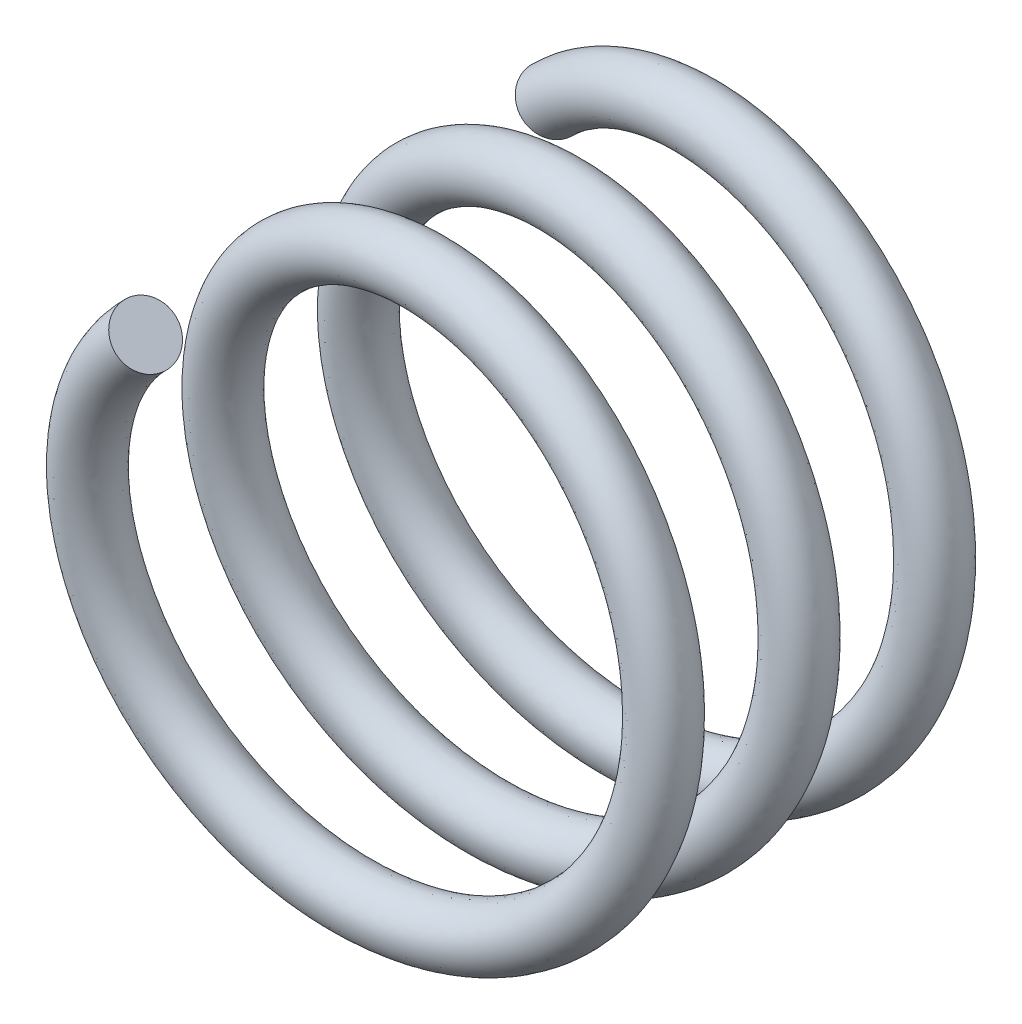
SolidWorks part; units mm, degrees
ref_plane "Front Plane" through (0, 0, 0) normal (0, 0, 1) x (1, 0, 0)
ref_plane "Top Plane" through (0, 0, 0) normal (0, 1, 0) x (1, 0, 0)
ref_plane "Right Plane" through (0, 0, 0) normal (1, 0, 0) x (0, 0, -1)
sketch "Sketch1" plane through (0, 0, 0) normal (0, 0, 1) x (1, 0, 0)
  circle A0 centre (0, 0) radius 4.36
  dimension "D1" = 8.72
curve "Helix/Spiral1" pitch 2.3333 height 7 radius 4.36 left hand yes centre (0, 0, 0) axis (0, 0, 1) start towards (-0.7071, 0.7071, 0)
ref_plane "Plane2" through (-3.083, 3.083, 0) normal (0.7046, 0.7046, 0.0849) x (0.7089, -0.6933, -0.1299)
sketch "Sketch3" plane through (-3.083, 3.083, 0) normal (0.7046, 0.7046, 0.0849) x (0.7089, -0.6933, -0.1299)
  circle A0 centre (0, 0) radius 0.5
sweep "Sweep1" add profiles "Sketch3" path "Helix/Spiral1"
ref_plane "Plane3" through (0, 0, 0) normal (0, 0, 1) x (1, 0, 0)
ref_plane "Plane4" through (0, 0, 7) normal (0, 0, 1) x (1, 0, 0)
ref_plane "Plane5" through (0, 0, 7.5) normal (0, 0, 1) x (1, 0, 0)
ref_plane "Plane6" through (0, 0, -0.5) normal (0, 0, 1) x (1, 0, 0)
equation "\"spring_diameter\"=8.72"
equation "\"coil_diameter\"=1.00"
equation "\"number_of_coils\"=3"
equation "\"D1@Sketch1\"=\"spring_diameter\""
equation "\"spring_length\"=7"
equation "\"D3@Helix/Spiral1\"=\"spring_length\""
equation "\"D1@Sketch3\"=\"coil_diameter\""
equation "\"D1@Plane5\"=\"coil_diameter\"/2"
equation "\"D1@Plane6\"=\"coil_diameter\"/2"
